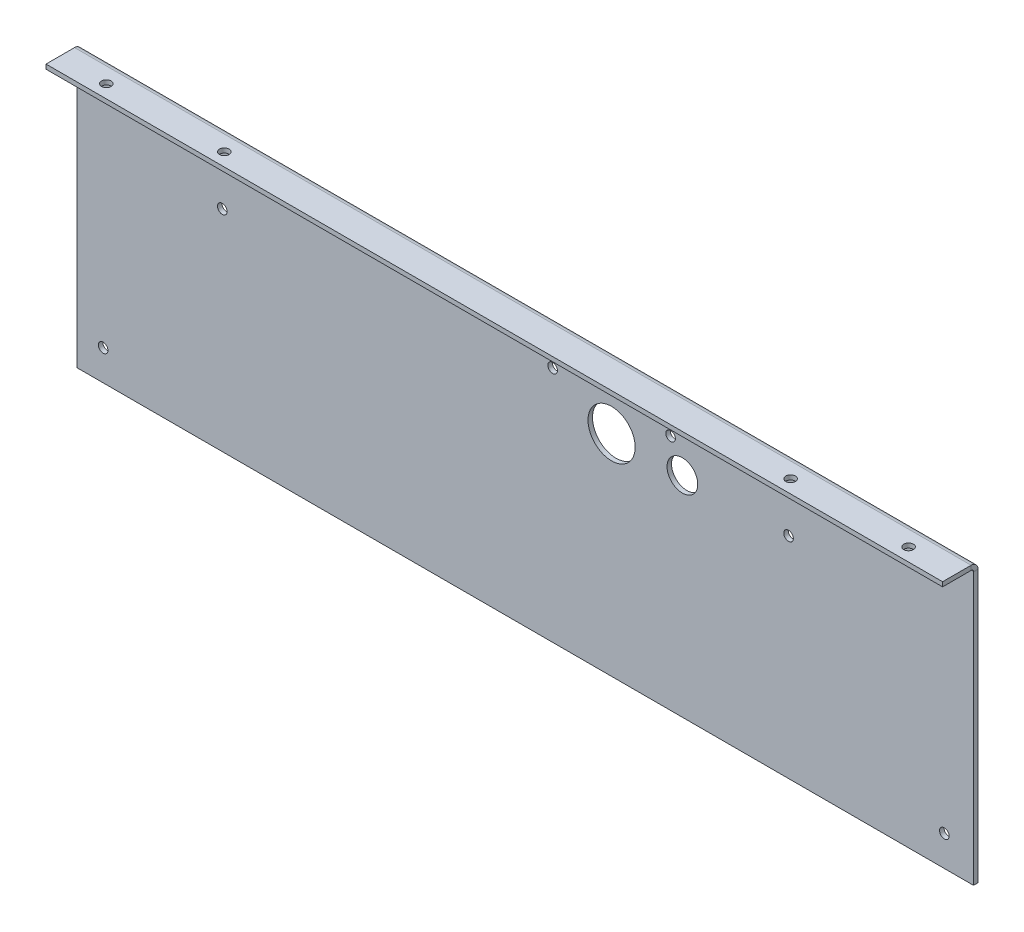
SolidWorks part; units mm, degrees
note: The reader was unsure of these and kept them because the rebuilt part matched: thickness of "Base-Flange1", "Edge-Flange1", "Sheet-Metal1", "Sheet-Metal2", "Sheet-Metal3", "Sheet-Metal4", "Sheet-Metal5", "Sheet-Metal6", "Sheet-Metal7"; flange length of "Edge-Flange1".
ref_plane "Front Plane" through (0, 0, 0) normal (0, 0, 1) x (1, 0, 0)
ref_plane "Top Plane" through (0, 0, 0) normal (0, 1, 0) x (1, 0, 0)
ref_plane "Right Plane" through (0, 0, 0) normal (1, 0, 0) x (0, 0, -1)
sketch "Sketch1" plane through (0, 0, 0) normal (0, 0, 1) x (1, 0, 0)
  line L1 (-190, 59) -> (190, 59)
  line L2 (-190, 59) -> (-190, -59)
  line L3 (-190, -59) -> (190, -59)
  line L4 (190, 59) -> (190, -59)
  line L5 (-190, 59) -> (190, -59) construction
  line L6 (-190, -59) -> (190, 59) construction
  point P0 (0, 0)
  dimension "D1" = 118
  dimension "D2" = 380
base flange "Base-Flange1" sketch "Sketch1" thickness 1.9 reverse thickness direction no parameters "D1"=1
edge flange "Edge-Flange1" sketch "Sketch8" flange angle 90 flange length 15 flange position material inside bend radius 1 thickness 1.9 relief rectangular parameters "D1"=1.9, "D6"=10
sketch "Sketch8" plane through (0, 59, 0) normal (0, 1, 0) x (-1, 0, 0)
  line L0 (-190, 0) -> (190, 0) construction
  line L1 (-190, 0) -> (190, 0)
  line L2 (-190, 0) -> (-190, 13.1)
  line L3 (-190, 13.1) -> (190, 13.1)
  line L4 (190, 13.1) -> (190, 0)
bend "EdgeBend1" bend radius 1 bend angle 90 parameters "D5"=1
sketch "Sketch9" plane through (0, 0, 0) normal (0, 0, 1) x (1, 0, 0)
  line L0 (-151.8373, 30.1) -> (149.6267, 30.1) construction
  line L1 (190, -59) -> (190, 56.1) construction
  line L2 (-190, 57.1) -> (190, 57.1) construction
  circle A0 centre (36.6107, 30.1) radius 10
  circle A3 centre (-128.3893, 30.1) radius 2.04
  circle A4 centre (111.6107, 30.1) radius 2.04
  dimension "D1" = 20
  dimension "D2" = 165
  dimension "D3" = 75
  dimension "D4" = 153.3893
  dimension "D5" = 27
  dimension "D6" = 4.08
  dimension "D7" = 4.08
extrude "Cut-Extrude1" cut sketch "Sketch9" against normal blind 10 normal cut yes
sketch "Sketch10" plane through (0, 57.1, 0) normal (0, -1, 0) x (1, 0, 0)
  line L0 (-190, 1) -> (-190, 13.1) construction
  line L1 (190, 13.1) -> (190, 1) construction
  circle A0 centre (-170, 7.5279) radius 2.04
  circle A1 centre (-120, 7.5279) radius 2.04
  circle A2 centre (170, 7.5279) radius 2.04
  circle A3 centre (120, 7.5279) radius 2.04
  dimension "D1" = 4.08
  dimension "D3" = 50
  dimension "D4" = 20
  dimension "D5" = 50
  dimension "D2" = 20
extrude "Cut-Extrude2" cut sketch "Sketch10" against normal blind 10 normal cut yes
sketch "Sketch11" plane through (0, 0, -1.9) normal (0, 0, -1) x (-1, 0, 0)
  circle A0 centre (178.8893, -46.1) radius 2.04
  circle A1 centre (-177.6525, -46.1) radius 2.04
  dimension "D1" = 4.08
extrude "Cut-Extrude3" cut sketch "Sketch11" against normal blind 10 normal cut yes
sketch "Sketch12" plane through (0, 0, 0) normal (0, 0, 1) x (1, 0, 0)
  circle A2 centre (11.6107, 41.7356) radius 2.04
  circle A3 centre (61.6107, 41.7356) radius 2.04
  dimension "D1" = 4.08
extrude "Cut-Extrude4" cut sketch "Sketch12" against normal blind 10 normal cut yes
sketch "Sketch13" plane through (0, 0, 0) normal (0, 0, 1) x (1, 0, 0)
  circle A0 centre (66.6107, 29.7738) radius 6.5
  circle A1 centre (36.6107, 30.1) radius 10 construction
  dimension "D1" = 30
extrude "Cut-Extrude5" cut sketch "Sketch13" against normal blind 62 normal cut yes
sketch "Bend-Lines1" [suppressed]
sketch "Bounding-Box1" [suppressed] plane through (0, 0, 0) normal (0, 1, 0) x (1, 0, 0)
sheet metal parameters "Sheet-Metal1" thickness 1.9 parameters "D1"=1
flat pattern "Flat-Pattern1" [suppressed]
sketch "Bend-Lines2" plane through (0, 0, 0) normal (0, 1, 0) x (1, 0, 0)
sketch "Bounding-Box2" [suppressed] plane through (0, 0, 0) normal (0, 1, 0) x (1, 0, 0)
sheet metal parameters "Sheet-Metal2" thickness 1.9 parameters "D1"=1, "D7"=1.2141
flat pattern "Flat-Pattern1" [suppressed]
sketch "Bend-Lines2" plane through (0, 0, 0) normal (0, 1, 0) x (1, 0, 0)
sketch "Bounding-Box2" [suppressed] plane through (0, 0, 0) normal (0, 1, 0) x (1, 0, 0)
bend of the flat pattern "Flatten-<EdgeBend1>1"
sheet metal parameters "Sheet-Metal3" thickness 1.9 parameters "D1"=1, "D7"=1.2141
flat pattern "Flat-Pattern1" [suppressed]
sketch "Bend-Lines2" plane through (0, 0, 0) normal (0, 1, 0) x (1, 0, 0)
sketch "Bounding-Box2" [suppressed] plane through (0, 0, 0) normal (0, 1, 0) x (1, 0, 0)
bend of the flat pattern "Flatten-<EdgeBend1>1"
sheet metal parameters "Sheet-Metal4" thickness 1.9 parameters "D1"=1, "D7"=1.2141
flat pattern "Flat-Pattern1" [suppressed]
sketch "Bend-Lines2" plane through (0, 0, 0) normal (0, 1, 0) x (1, 0, 0)
sketch "Bounding-Box2" [suppressed] plane through (0, 0, 0) normal (0, 1, 0) x (1, 0, 0)
bend of the flat pattern "Flatten-<EdgeBend1>1"
sheet metal parameters "Sheet-Metal5" thickness 1.9 parameters "D1"=1, "D7"=1.2141
flat pattern "Flat-Pattern1"
sketch "Bend-Lines2" plane through (0, 0, 0) normal (0, 0, 1) x (1, 0, 0)
  line L0 (190, 57.6315) -> (-190, 57.6315) construction
  line L1 (190, 57.6315) -> (-190, 57.6315) construction
sketch3d "Bounding-Box2" [suppressed]
  line L0 (-190, -59, 0) -> (190, -59, 0) construction
  line L1 (-190, 71.2631, 0) -> (190, 71.2631, 0) construction
  line L2 (-190, -59, 0) -> (-190, 71.2631, 0) construction
  line L3 (190, -59, 0) -> (190, 71.2631, 0) construction
bend of the flat pattern "Flatten-<EdgeBend1>1"
sheet metal parameters "Sheet-Metal6" thickness 1.9 parameters "D1"=1, "D7"=1.2141
flat pattern "Flat-Pattern1"
sketch "Bend-Lines2" plane through (0, 0, 0) normal (0, 0, 1) x (1, 0, 0)
  line L0 (190, 57.6315) -> (-190, 57.6315) construction
  line L1 (190, 57.6315) -> (-190, 57.6315) construction
sketch3d "Bounding-Box2" [suppressed]
  line L0 (-190, -59, 0) -> (190, -59, 0) construction
  line L1 (-190, 71.2631, 0) -> (190, 71.2631, 0) construction
  line L2 (-190, -59, 0) -> (-190, 71.2631, 0) construction
  line L3 (190, -59, 0) -> (190, 71.2631, 0) construction
bend of the flat pattern "Flatten-<EdgeBend1>1"
sheet metal parameters "Sheet-Metal7" thickness 1.9 parameters "D1"=1, "D7"=1.2141
flat pattern "Flat-Pattern1"
sketch "Bend-Lines2" plane through (0, 0, 0) normal (0, 0, 1) x (1, 0, 0)
  line L0 (190, 57.6315) -> (-190, 57.6315) construction
  line L1 (190, 57.6315) -> (-190, 57.6315) construction
sketch3d "Bounding-Box2" [suppressed]
  line L0 (-190, -59, 0) -> (190, -59, 0) construction
  line L1 (-190, 71.2631, 0) -> (190, 71.2631, 0) construction
  line L2 (-190, -59, 0) -> (-190, 71.2631, 0) construction
  line L3 (190, -59, 0) -> (190, 71.2631, 0) construction
bend of the flat pattern "Flatten-<EdgeBend1>1"
